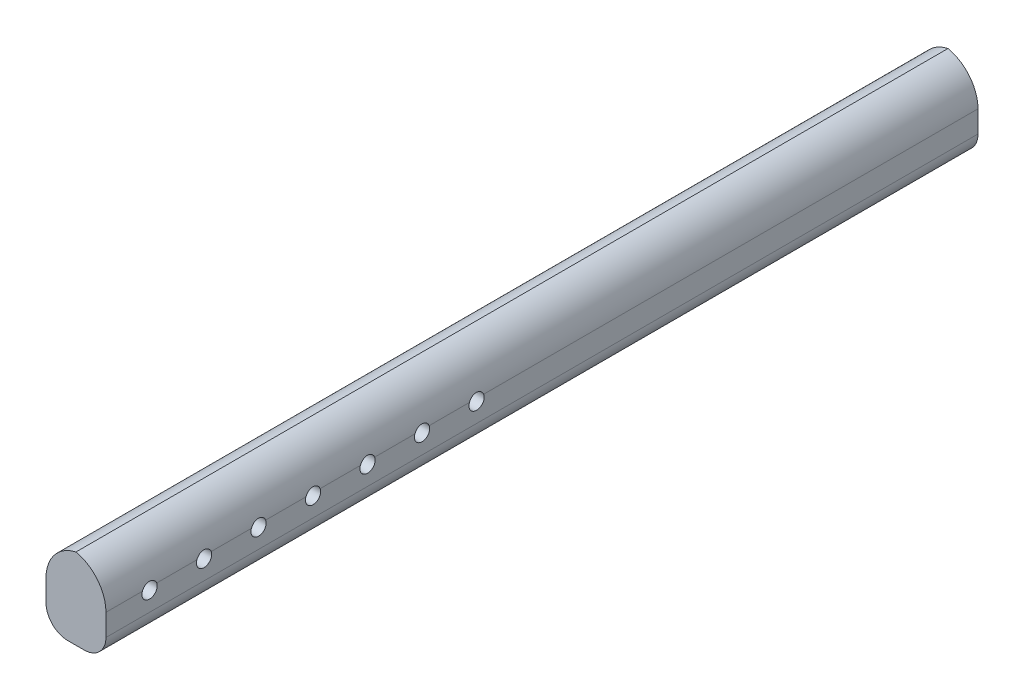
SolidWorks part; units mm, degrees
ref_plane "Plan de face" through (0, 0, 0) normal (0, 0, 1) x (1, 0, 0)
ref_plane "Plan de dessus" through (0, 0, 0) normal (0, 1, 0) x (1, 0, 0)
ref_plane "Plan de droite" through (0, 0, 0) normal (1, 0, 0) x (0, 0, -1)
sketch "Esquisse1" plane through (0, 0, 0) normal (0, 0, 1) x (1, 0, 0)
  line L1 (2.75, 3.75) -> (-2.75, 3.75)
  line L2 (2.75, 3.75) -> (2.75, -3.75)
  line L3 (2.75, -3.75) -> (-2.75, -3.75)
  line L4 (-2.75, 3.75) -> (-2.75, -3.75)
  line L5 (2.75, 3.75) -> (-2.75, -3.75) construction
  line L6 (2.75, -3.75) -> (-2.75, 3.75) construction
  point P0 (0, 0)
  dimension "D1" = 5.5
  dimension "D2" = 7.5
extrude "Boss.-Extru.1" add sketch "Esquisse1" along normal blind 80
fillet "Congé1" radius 3.5 2 edges at (-2.75, 3.75, 40) (2.75, 3.75, 40)
fillet "Congé2" radius 2 2 edges at (2.75, -3.75, 40) (-2.75, -3.75, 40)
sketch "Esquisse2" plane through (-2.75, 0, 0) normal (-1, 0, 0) x (0, 0, 1)
  line L0 (0, 0) -> (80, 0) construction
  line L1 (80, 0.25) -> (80, -1.75) construction
  circle A0 centre (46, 0) radius 0.7
  circle A1 centre (51, 0) radius 0.7
  circle A2 centre (56, 0) radius 0.7
  circle A3 centre (61, 0) radius 0.7
  circle A4 centre (66, 0) radius 0.7
  circle A5 centre (71, 0) radius 0.7
  circle A6 centre (76, 0) radius 0.7
  dimension "D1" = 1.4
  dimension "D2" = 46
  dimension "D3" = 7
extrude "Enlèv. mat.-Extru.1" cut sketch "Esquisse2" against normal through all
